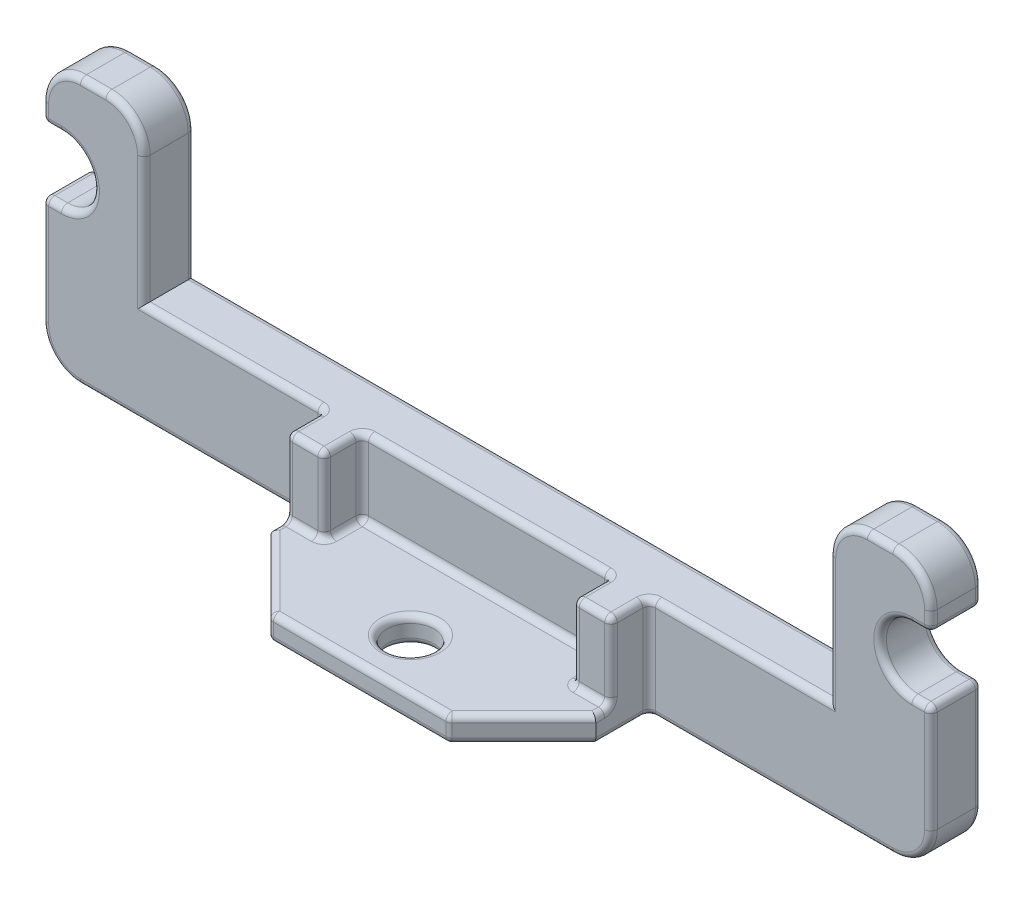
SolidWorks part; units mm, degrees
ref_plane "Front Plane" through (0, 0, 0) normal (0, 0, 1) x (1, 0, 0)
ref_plane "Top Plane" through (0, 0, 0) normal (0, 1, 0) x (1, 0, 0)
ref_plane "Right Plane" through (0, 0, 0) normal (1, 0, 0) x (0, 0, -1)
sketch "Sketch1" plane through (0, 0, 0) normal (0, 0, 1) x (1, 0, 0)
  line L0 (-27, 4.0307) -> (-27, 17.0307)
  line L1 (-27, 4.0307) -> (27, 4.0307)
  line L3 (-35, -3.9693) -> (35, -3.9693)
  line L5 (-34.0198, 3.8581) -> (35, -3.9693) construction
  line L6 (-35, -3.9693) -> (32.7854, 3.7181) construction
  line L8 (-35, -3.9693) -> (-35, 17.0307)
  line L9 (-35, 17.0307) -> (-27, 17.0307)
  line L12 (35, -3.9693) -> (35, 17.0307)
  line L13 (35, 17.0307) -> (27, 17.0307)
  line L15 (27, 4.0307) -> (27, 17.0307)
  point P0 (0, 0)
  dimension "D1" = 35
  dimension "D3" = 8
  dimension "D4" = 8
  dimension "D5" = 8
  dimension "D6" = 13
  dimension "D7" = 35
  dimension "D8" = 13
extrude "Boss-Extrude1" add sketch "Sketch1" along normal blind 4
sketch "Sketch2" plane through (0, 0, 4) normal (0, 0, 1) x (1, 0, 0)
  line L0 (-35, 17.0307) -> (-35, -3.9693) construction
  line L3 (-35, 10.0307) -> (41.6211, 10.0307) construction
  line L4 (35, 10.0307) -> (33.4949, 10.0307) construction
  line L5 (35, -3.9693) -> (35, 17.0307) construction
  line L6 (35, 7.5307) -> (33.4949, 7.5307)
  line L7 (35, 12.5307) -> (33.4949, 12.5307)
  line L8 (0, 0) -> (0, 23.7087) construction
  line L9 (-35, 10.0307) -> (-33.4949, 10.0307) construction
  line L10 (-35, 7.5307) -> (-33.4949, 7.5307)
  line L11 (-35, 12.5307) -> (-33.4949, 12.5307)
  line L13 (27, 4.0307) -> (-27, 4.0307) construction
  arc A0 (35, 7.5307) -> (35, 12.5307) centre (35, 10.0307) ccw
  arc A1 (33.4949, 12.5307) -> (33.4949, 7.5307) centre (33.4949, 10.0307) ccw
  arc A2 (-35, 7.5307) -> (-35, 12.5307) centre (-35, 10.0307) cw
  arc A3 (-33.4949, 12.5307) -> (-33.4949, 7.5307) centre (-33.4949, 10.0307) cw
  point P9 (34.2474, 10.0307)
  point P20 (-34.2474, 10.0307)
  dimension "D1" = 6
extrude "Cut-Extrude1" cut sketch "Sketch2" against normal blind 6
sketch "Sketch3" plane through (0, 0, 4) normal (0, 0, 1) x (1, 0, 0)
  line L0 (-35, -3.9693) -> (35, -3.9693) construction
  line L1 (-7, -3.9693) -> (7, -3.9693)
  line L2 (-7, -3.9693) -> (-7, -1.9693)
  line L3 (-7, -1.9693) -> (7, -1.9693)
  line L4 (7, -3.9693) -> (7, -1.9693)
  dimension "D1" = 2
  dimension "D2" = 7
  dimension "D3" = 7
extrude "Boss-Extrude2" add sketch "Sketch3" along normal blind 10
sketch "Sketch4" plane through (0, -1.9693, 0) normal (0, 1, 0) x (1, 0, 0)
  line L0 (7, -4) -> (-7, -4) construction
  circle A0 centre (0, -10) radius 1.85
  dimension "D1" = 6
extrude "Cut-Extrude2" cut sketch "Sketch4" against normal blind 10
sketch "Sketch5" plane through (0, -1.9693, 0) normal (0, 1, 0) x (1, 0, 0)
  line L0 (7, -14) -> (12.8, -8.2)
  line L2 (-7, -14) -> (-12.8, -8.2)
  line L3 (-12.8, -4) -> (-7, -4)
  line L4 (-7, -4) -> (-7, -14)
  line L5 (7, -14) -> (7, -4)
  line L6 (7, -4) -> (12.8, -4)
  line L7 (-12.8, -4) -> (-12.8, -8.2)
  line L8 (12.8, -4) -> (12.8, -8.2)
extrude "Boss-Extrude3" add sketch "Sketch5" against normal blind 2
sketch "Sketch6" plane through (0, -1.9693, 0) normal (0, 1, 0) x (1, 0, 0)
  line L0 (12.8, -4) -> (-12.8, -4) construction
  line L1 (-12.8, -4) -> (-9.8, -4)
  line L2 (-12.8, -4) -> (-12.8, -7)
  line L3 (-12.8, -7) -> (-9.8, -7)
  line L4 (-9.8, -4) -> (-9.8, -7)
  line L5 (0, 0) -> (0, -25.9918) construction
  line L6 (9.8, -4) -> (9.8, -7)
  line L7 (12.8, -4) -> (9.8, -4)
  line L8 (12.8, -4) -> (12.8, -7)
  line L9 (12.8, -7) -> (9.8, -7)
  circle A0 centre (0, -10) radius 5 construction
  dimension "D1" = 3
  dimension "D2" = 3
  dimension "D3" = 9.8
extrude "Boss-Extrude4" add sketch "Sketch6" along normal up to surface (6 mm away) up to face at (0, 4.0307, 2)
fillet "Fillet1" radius 3 6 edges at (-35, -3.9693, 2) (35, -3.9693, 2) (35, 17.0307, 2) (27, 17.0307, 2) (-35, 17.0307, 2) (-27, 17.0307, 2)
fillet "Fillet3" radius 0.5 80 edges at (-9.8, 4.0307, 5.5) (9.8, 4.0307, 5.5) (12.8, 4.0307, 5.5) (-12.8, 4.0307, 5.5) (35, 13.2807, 0) (34.1213, 16.1521, 0) (31, 17.0307, 0) (27.8787, 16.1521, 0) (27, 9.0307, 0) (0, 4.0307, 0) (-27, 9.0307, 0) (-27.8787, 16.1521, 0) (-31, 17.0307, 0) (-34.1213, 16.1521, 0) (-35, 13.2807, 0) (-35, 3.2807, 0) (-34.1213, -3.0906, 0) (34.1213, -3.0906, 0) (35, 3.2807, 0) (0, -3.9693, 11.85) (-12.8, -3.9693, 6.1) (-9.9, -3.9693, 11.1) (9.9, -3.9693, 11.1) (12.8, -3.9693, 6.1) (0, -3.9693, 0) (7, -2.9693, 14) (0, -3.9693, 14) (-7, -2.9693, 14) (12.8, -1.9693, 7.6) (9.9, -1.9693, 11.1) (0, -1.9693, 14) (-9.9, -1.9693, 11.1) (-12.8, -1.9693, 7.6) (-9.8, -1.9693, 5.5) (9.8, -1.9693, 5.5) (0, -1.9693, 11.85) (11.3, -1.9693, 7) (9.8, 1.0307, 7) (11.3, 4.0307, 7) (12.8, 1.0307, 7) (-11.3, -1.9693, 7) (-12.8, 1.0307, 7) (-11.3, 4.0307, 7) (-9.8, 1.0307, 7) (-9.8, 1.0307, 4) (0, 4.0307, 4) (9.8, 1.0307, 4) (0, -1.9693, 4) (34.1213, -3.0906, 4) (12.8, 0.0307, 4) (19.9, 4.0307, 4) (27, 9.0307, 4) (27.8787, 16.1521, 4) (31, 17.0307, 4) (34.1213, 16.1521, 4) (35, 13.2807, 4) (35, 3.2807, 4) (-35, 13.2807, 4) (-34.1213, 16.1521, 4) (-31, 17.0307, 4) (-27.8787, 16.1521, 4) (-27, 9.0307, 4) (-19.9, 4.0307, 4) (-12.8, 0.0307, 4) (-34.1213, -3.0906, 4) (-35, 3.2807, 4) (34.2474, 7.5307, 0) (30.9949, 10.0307, 0) (34.2474, 12.5307, 0) (-34.2474, 12.5307, 0) (-30.9949, 10.0307, 0) (-34.2474, 7.5307, 0) (34.2474, 12.5307, 4) (30.9949, 10.0307, 4) (34.2474, 7.5307, 4) (-34.2474, 7.5307, 4) (-30.9949, 10.0307, 4) (-34.2474, 12.5307, 4)
fillet "Fillet4" radius 0.5 12 edges at (34.8536, 7.3843, 0.1464) (34.8536, 7.3843, 3.8536) (34.8536, 12.6772, 0.1464) (34.8536, 12.6772, 3.8536) (-34.8536, 7.3843, 0.1464) (-34.8536, 7.3843, 3.8536) (-34.8536, 12.6772, 0.1464) (-34.8536, 12.6772, 3.8536) (35, 7.5307, 2) (35, 12.5307, 2) (-35, 7.5307, 2) (-35, 12.5307, 2)
sketch "Sketch7" plane through (0, -3.9693, 0) normal (0, -1, 0) x (1, 0, 0)
  line L0 (-9.2331, 2) -> (9.3768, 2) construction
  line L1 (0, 10) -> (6.8619, 10) construction
  line L2 (0, 0) -> (0, 10) construction
  line L3 (-3.8987, 1.9) -> (3.8987, 1.9)
  arc A0 (-3.8987, 1.9) -> (3.8987, 1.9) centre (0, 2) ccw
  dimension "D2" = 0.1
  dimension "D1" = 8
extrude "Boss-Extrude5" add sketch "Sketch7" along normal mid plane 4
fillet "Fillet6" radius 0.5 2 edges at (0, -1.9693, -1.9) (0, -5.9693, -1.9)
